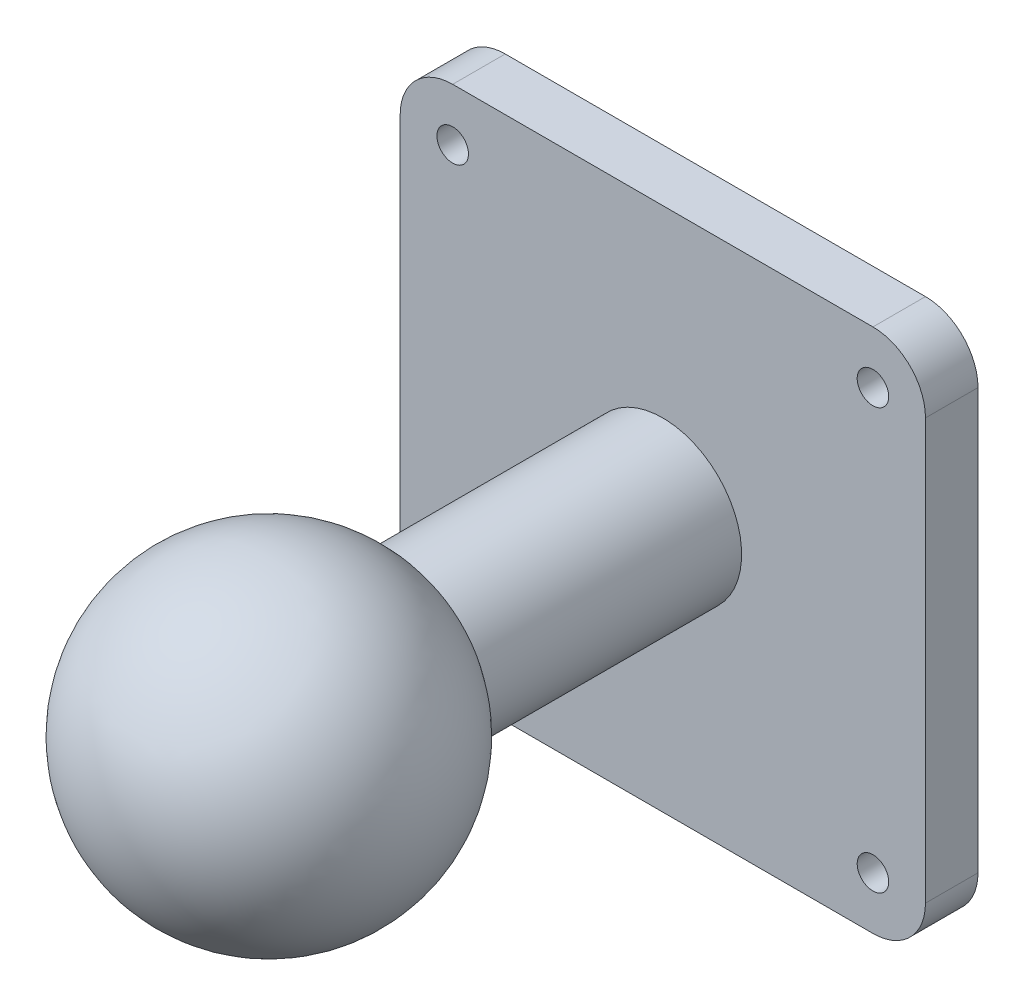
SolidWorks part; units mm, degrees
ref_plane "Alzado" through (0, 0, 0) normal (0, 0, 1) x (1, 0, 0)
ref_plane "Planta" through (0, 0, 0) normal (0, 1, 0) x (1, 0, 0)
ref_plane "Vista lateral" through (0, 0, 0) normal (1, 0, 0) x (0, 0, -1)
sketch "Croquis1" plane through (0, 0, 0) normal (0, 0, 1) x (1, 0, 0)
  line L1 (-25, -25) -> (25, -25)
  line L2 (-25, -25) -> (-25, 25)
  line L3 (-25, 25) -> (25, 25)
  line L4 (25, -25) -> (25, 25)
  line L5 (-25, -25) -> (25, 25) construction
  line L6 (-25, 25) -> (25, -25) construction
  point P0 (0, 0)
  dimension "D1" = 50
  dimension "D2" = 50
extrude "Saliente-Extruir1" add sketch "Croquis1" along normal blind 5
sketch "Croquis2" plane through (0, 0, 5) normal (0, 0, 1) x (1, 0, 0)
  circle A0 centre (0, 0) radius 7.5
  dimension "D1" = 15
ref_plane "Plano1" through (0, 0, 42.5) normal (0, 0, 1) x (1, 0, 0)
sketch "Croquis3" plane through (0, 0, 42.5) normal (0, 0, 1) x (1, 0, 0)
  line L0 (0, 15) -> (0, -15) construction
  line L1 (0, 15) -> (0, -15)
  arc A0 (0, -15) -> (0, 15) centre (0, 0) ccw
  dimension "D1" = 30
revolve "Revolución1" add sketch "Croquis3" angle 360 about L0
extrude "Saliente-Extruir2" add sketch "Croquis2" along normal up to surface (24.5096 mm away) contours A0
sketch "Croquis4" plane through (0, 0, 5) normal (0, 0, 1) x (1, 0, 0)
  line L0 (0, 25) -> (0, 0) construction
  line L1 (25, 25) -> (-25, 25) construction
  line L2 (0, 0) -> (25, 0) construction
  line L3 (25, -25) -> (25, 25) construction
  line L4 (-25, 25) -> (-25, -25) construction
  circle A0 centre (-20, 20) radius 1.5
  circle A1 centre (20, 20) radius 1.5
  circle A2 centre (20, -20) radius 1.5
  circle A3 centre (-20, -20) radius 1.5
  dimension "D1" = 3
  dimension "D3" = 5
  dimension "D2" = 5
extrude "Cortar-Extruir1" cut sketch "Croquis4" against normal blind 5
fillet "Redondeo1" radius 5 4 edges at (25, -25, 2.5) (25, 25, 2.5) (-25, 25, 2.5) (-25, -25, 2.5)
